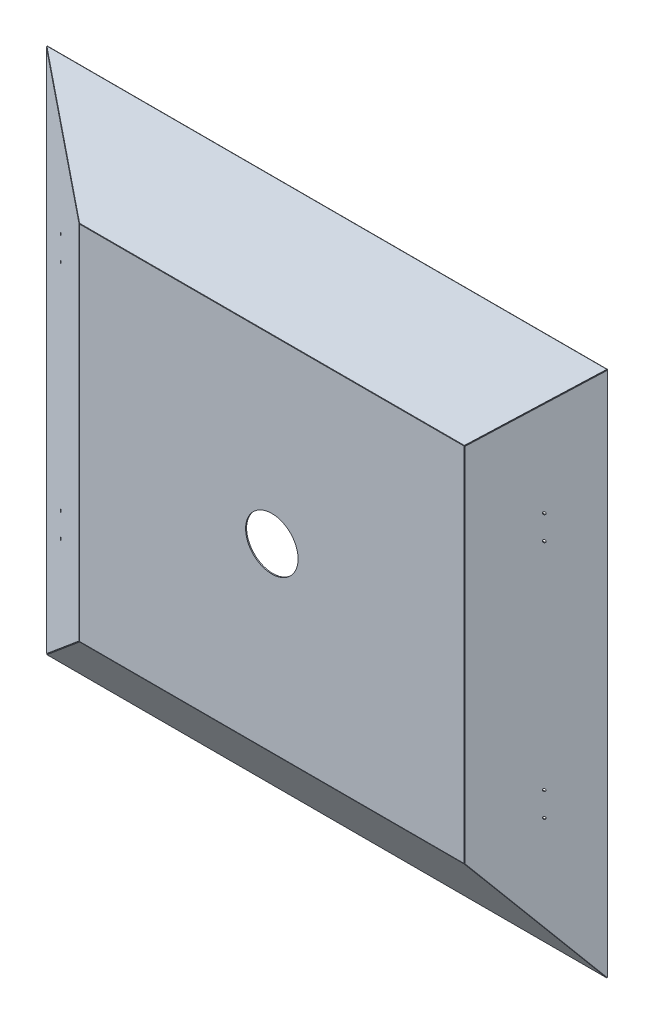
SolidWorks part; units mm, degrees
material "Pine"
ref_plane "Front Plane" through (0, 0, 0) normal (0, 0, 1) x (1, 0, 0)
ref_plane "Top Plane" through (0, 0, 0) normal (0, 1, 0) x (1, 0, 0)
ref_plane "Right Plane" through (0, 0, 0) normal (1, 0, 0) x (0, 0, -1)
sketch "Sketch1" plane through (0, 0, 0) normal (0, 0, 1) x (1, 0, 0)
  line L0 (724, -500) -> (724, 500) construction
  line L1 (-724, 680) -> (724, 680)
  line L2 (-724, 680) -> (-724, -680)
  line L3 (-724, -680) -> (724, -680)
  line L4 (724, 680) -> (724, -680)
  line L5 (-724, 680) -> (724, -680) construction
  line L6 (-724, -680) -> (724, 680) construction
  line L7 (675, -680) -> (-675, -680) construction
  point P0 (0, 0)
ref_axis "Axis1" through (0, 0, 80.9) along (0, 0, -1)
ref_plane "Plane4" through (0, 0, 100) normal (0, 0, 1) x (1, 0, 0)
sketch "Sketch2" plane through (0, 0, 100) normal (0, 0, 1) x (1, 0, 0)
  line L0 (-724, 680) -> (724, 680) construction
  line L1 (-564.2941, -530) -> (564.2941, -530)
  line L2 (-564.2941, -530) -> (-564.2941, 530)
  line L3 (-564.2941, 530) -> (564.2941, 530)
  line L4 (564.2941, -530) -> (564.2941, 530)
  line L5 (-564.2941, -530) -> (564.2941, 530) construction
  line L6 (-564.2941, 530) -> (564.2941, -530) construction
  line L7 (-724, -680) -> (724, 680) construction
  point P0 (0, 0)
  dimension "D1" = 150
ref_axis "Axis2" through (-724, 680, 0) along (0.6631, -0.6228, 0.4152)
ref_axis "Axis3" through (564.2941, 530, 100) along (0.6631, 0.6228, -0.4152)
ref_axis "Axis4" through (564.2941, -530, 100) along (0.6631, -0.6228, -0.4152)
ref_axis "Axis5" through (-564.2941, -530, 100) along (-0.6631, -0.6228, -0.4152)
ref_plane "Plane5" through (0, -209.2308, 313.8462) normal (0, -0.5547, 0.8321) x (1, 0, 0)
ref_plane "Plane6" through (203.9094, 0, 325.6553) normal (0.5307, 0, 0.8476) x (0.8476, 0, -0.5307)
ref_plane "Plane7" through (0, 209.2308, 313.8462) normal (0, -0.5547, -0.8321) x (-1, 0, 0)
ref_plane "Plane8" through (-203.9094, 0, 325.6553) normal (0.5307, 0, -0.8476) x (-0.8476, 0, -0.5307)
sketch "Sketch3" plane through (0, -209.2308, 313.8462) normal (0, -0.5547, 0.8321) x (1, 0, 0)
  line L0 (-724, -565.7942) -> (724, -565.7942) construction
  line L1 (-564.2941, -385.5166) -> (564.2941, -385.5166) construction
  line L2 (-724, -565.7942) -> (724, -565.7942) construction
  line L3 (-564.2941, -385.5166) -> (564.2941, -385.5166)
  line L4 (-564.2941, -385.5166) -> (-724, -565.7942)
  line L5 (564.2941, -385.5166) -> (724, -565.7942)
  line L6 (-724, -565.7942) -> (-821.2019, -675.5166)
  line L7 (-821.2019, -675.5166) -> (821.2019, -675.5166)
  line L8 (821.2019, -675.5166) -> (724, -565.7942)
  dimension "D1" = 290
extrude "Boss-Extrude1" add sketch "Sketch3" along normal blind 3
sketch "Sketch4" plane through (-203.9094, 0, 325.6553) normal (0.5307, 0, -0.8476) x (-0.8476, 0, -0.5307)
  line L0 (613.6331, 680) -> (613.6331, -680) construction
  line L1 (613.6331, 680) -> (613.6331, -680) construction
  line L2 (425.2028, -530) -> (425.2028, 530) construction
  line L3 (425.2028, -530) -> (425.2028, 530)
  line L4 (425.2028, -530) -> (728.3175, -771.2946)
  line L5 (728.3175, -771.2946) -> (728.3175, 771.2946)
  line L6 (728.3175, 771.2946) -> (425.2028, 530)
  line L7 (613.6331, 680) -> (425.2028, 530) construction
extrude "Boss-Extrude2" add sketch "Sketch4" against normal blind 3 separate body
sketch "Sketch5" plane through (203.9094, 0, 325.6553) normal (0.5307, 0, 0.8476) x (0.8476, 0, -0.5307)
  line L0 (613.6331, 680) -> (613.6331, -680) construction
  line L1 (425.2028, -530) -> (425.2028, 530) construction
  line L2 (613.6331, 680) -> (613.6331, -680) construction
  line L3 (425.2028, -530) -> (425.2028, 530)
  line L4 (728.3175, -771.2946) -> (425.2028, -530)
  line L5 (425.2028, 530) -> (728.3175, 771.2946)
  line L6 (728.3175, 771.2946) -> (728.3175, -771.2946)
  line L7 (425.2028, 530) -> (613.6331, 680) construction
extrude "Boss-Extrude3" add sketch "Sketch5" along normal blind 3 separate body
sketch "Sketch6" plane through (0, 209.2308, 313.8462) normal (0, -0.5547, -0.8321) x (-1, 0, 0)
  line L0 (-564.2941, 385.5166) -> (564.2941, 385.5166)
  line L1 (564.2941, 385.5166) -> (821.2019, 675.5166)
  line L2 (821.2019, 675.5166) -> (-821.2019, 675.5166)
  line L3 (-821.2019, 675.5166) -> (-564.2941, 385.5166)
extrude "Boss-Extrude4" add sketch "Sketch6" against normal blind 3 separate body
ref_plane "Plane9" through (0, 0, 100) normal (0, 0, 1) x (1, 0, 0)
sketch "Sketch7" plane through (0, 0, 100) normal (0, 0, 1) x (1, 0, 0)
  line L1 (-564.2941, -530) -> (564.2941, -530)
  line L2 (-564.2941, -530) -> (-564.2941, 530)
  line L3 (-564.2941, 530) -> (564.2941, 530)
  line L4 (564.2941, -530) -> (564.2941, 530)
extrude "Boss-Extrude5" add sketch "Sketch7" along normal blind 3 separate body
sketch "Sketch9" plane through (203.9094, 0, 325.6553) normal (-0.5307, 0, -0.8476) x (-0.8476, 0, 0.5307)
  circle A0 centre (-593.9973, 387) radius 4
  circle A1 centre (-593.9973, 316) radius 4
  circle A2 centre (-593.9973, -316) radius 4
  circle A3 centre (-593.9973, -387) radius 4
  dimension "D2" = 8
extrude "Cut-Extrude2" cut sketch "Sketch9" against normal through all
sketch "Sketch10" plane through (-203.9094, 0, 325.6553) normal (0.5307, 0, -0.8476) x (-0.8476, 0, -0.5307)
  circle A0 centre (593.9973, -387) radius 4
  circle A1 centre (593.9973, -316) radius 4
  circle A2 centre (593.9973, 316) radius 4
  circle A3 centre (593.9973, 387) radius 4
  dimension "D1" = 8
extrude "Cut-Extrude3" cut sketch "Sketch10" against normal through all
sketch "Sketch11" plane through (0, 0, 103) normal (0, 0, 1) x (1, 0, 0)
  circle A0 centre (0, 0) radius 75 construction
  circle A1 centre (0, 0) radius 75 construction
  circle A2 centre (0, 0) radius 77
  dimension "D1" = 2
extrude "Cut-Extrude4" cut sketch "Sketch11" against normal through all
